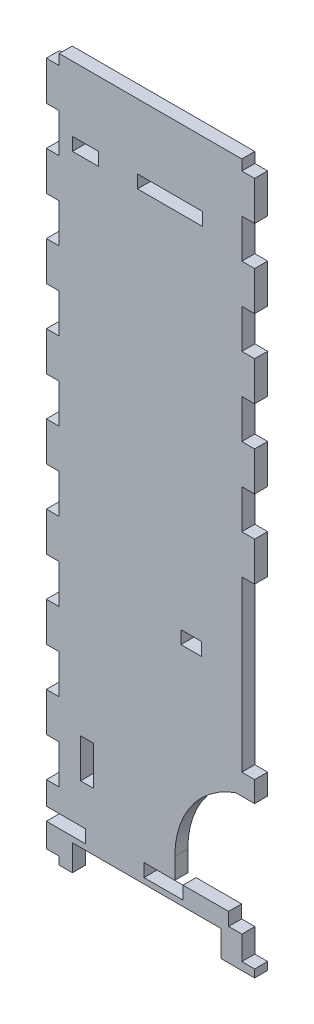
SolidWorks part; units mm, degrees
material "Balsa"
ref_plane "Plan de face" through (0, 0, 0) normal (0, 0, 1) x (1, 0, 0)
ref_plane "Plan de dessus" through (0, 0, 0) normal (0, 1, 0) x (1, 0, 0)
ref_plane "Plan de droite" through (0, 0, 0) normal (1, 0, 0) x (0, 0, -1)
sketch "Esquisse1" plane through (0, 0, 0) normal (0, 0, 1) x (1, 0, 0)
  line L0 (49.3309, 25.1093) -> (120.4109, 25.1093) construction
  line L1 (0, 0) -> (80, 0)
  line L2 (0, 0) -> (0, 270)
  line L3 (0, 270) -> (80, 270)
  line L4 (80, 59.7791) -> (80, 270)
  line L5 (49.3309, 25.1093) -> (49.3309, 17.15)
  line L6 (49.3309, 17.15) -> (80, 17.15)
  line L7 (80, 17.15) -> (80, 0)
  ellipse E0 centre (84.8709, 25.1093) end of major axis (120.4109, 25.1093) minor radius 35 (49.3309, 25.1093) -> (80, 59.7791) cw
  point P5 (84.8709, 25.1093)
  dimension "D1" = 80
  dimension "D2" = 270
  dimension "D3" = 80
  dimension "D4" = 70
  dimension "D5" = 71.08
extrude "Boss.-Extru.1" add sketch "Esquisse1" along normal blind 5
sketch "Esquisse2" plane through (0, 0, 5) normal (0, 0, 1) x (1, 0, 0)
  line L0 (80, 0) -> (80, 17.15) construction
  line L1 (51.6797, 101.7504) -> (59.6797, 101.7504)
  line L2 (51.6797, 101.7504) -> (51.6797, 96.7504)
  line L3 (51.6797, 96.7504) -> (59.6797, 96.7504)
  line L4 (59.6797, 101.7504) -> (59.6797, 96.7504)
  line L5 (75.08, 12.15) -> (70, 12.15)
  line L6 (80, 17.15) -> (80, 3)
  line L7 (80, 3) -> (75.08, 3)
  line L8 (75.08, 12.15) -> (75.08, 3)
  line L9 (80, 59.7791) -> (80, 270) construction
  line L10 (0, 0) -> (80, 0) construction
  line L11 (70, 12.15) -> (70, 17.15)
  line L12 (80, 17.15) -> (49.3309, 17.15) construction
  line L13 (70, 17.15) -> (80, 17.15)
  line L14 (0, 270) -> (0, 0) construction
  line L15 (37.5, 17.15) -> (52.5, 17.15)
  line L16 (37.5, 17.15) -> (37.5, 12.15)
  line L17 (37.5, 12.15) -> (52.5, 12.15)
  line L18 (52.5, 17.15) -> (52.5, 12.15)
  line L19 (15, 17.15) -> (0, 17.15)
  line L20 (15, 17.15) -> (15, 12.15)
  line L21 (15, 12.15) -> (0, 12.15)
  line L22 (0, 17.15) -> (0, 12.15)
  line L23 (80, 131) -> (75.08, 131)
  line L24 (0, 0) -> (4.92, 0)
  line L25 (0, 0) -> (0, 3)
  line L26 (0, 3) -> (4.92, 3)
  line L27 (4.92, 0) -> (4.92, 3)
  line L28 (80, 131) -> (80, 66)
  line L29 (80, 66) -> (75.08, 66)
  line L30 (75.08, 131) -> (75.08, 66)
  line L31 (0, 0) -> (80, 0) construction
  line L32 (80, 191) -> (75.08, 191)
  line L33 (80, 161) -> (75.08, 161)
  line L34 (80, 161) -> (80, 146)
  line L35 (80, 146) -> (75.08, 146)
  line L36 (75.08, 161) -> (75.08, 146)
  line L37 (80, 191) -> (80, 176)
  line L38 (80, 176) -> (75.08, 176)
  line L39 (75.08, 191) -> (75.08, 176)
  line L40 (80, 221) -> (75.08, 221)
  line L41 (80, 221) -> (80, 206)
  line L42 (80, 206) -> (75.08, 206)
  line L43 (75.08, 221) -> (75.08, 206)
  line L44 (80, 251) -> (75.08, 251)
  line L45 (80, 251) -> (80, 236)
  line L46 (80, 236) -> (75.08, 236)
  line L47 (75.08, 251) -> (75.08, 236)
  line L48 (80, 281) -> (75.08, 281)
  line L49 (80, 281) -> (80, 266)
  line L50 (80, 266) -> (75.08, 266)
  line L51 (75.08, 281) -> (75.08, 266)
  line L52 (0, 270) -> (0, 0) construction
  line L53 (0, 266) -> (4.92, 266)
  line L54 (0, 266) -> (0, 281)
  line L55 (0, 281) -> (4.92, 281)
  line L56 (4.92, 266) -> (4.92, 281)
  line L57 (80, 270) -> (0, 270) construction
  line L58 (0, 236) -> (4.92, 236)
  line L59 (0, 236) -> (0, 251)
  line L60 (0, 251) -> (4.92, 251)
  line L61 (4.92, 236) -> (4.92, 251)
  line L62 (0, 206) -> (4.92, 206)
  line L63 (0, 206) -> (0, 221)
  line L64 (0, 221) -> (4.92, 221)
  line L65 (4.92, 206) -> (4.92, 221)
  line L66 (0, 176) -> (4.92, 176)
  line L67 (0, 176) -> (0, 191)
  line L68 (0, 191) -> (4.92, 191)
  line L69 (4.92, 176) -> (4.92, 191)
  line L70 (0, 146) -> (4.92, 146)
  line L71 (0, 146) -> (0, 161)
  line L72 (0, 161) -> (4.92, 161)
  line L73 (4.92, 146) -> (4.92, 161)
  line L74 (0, 116) -> (4.92, 116)
  line L75 (0, 116) -> (0, 131)
  line L76 (0, 131) -> (4.92, 131)
  line L77 (4.92, 116) -> (4.92, 131)
  line L78 (0, 86) -> (4.92, 86)
  line L79 (0, 86) -> (0, 101)
  line L80 (0, 101) -> (4.92, 101)
  line L81 (4.92, 86) -> (4.92, 101)
  line L82 (0, 56) -> (4.92, 56)
  line L83 (0, 56) -> (0, 71)
  line L84 (0, 71) -> (4.92, 71)
  line L85 (4.92, 56) -> (4.92, 71)
  line L86 (0, 26) -> (4.92, 26)
  line L87 (0, 26) -> (0, 41)
  line L88 (0, 41) -> (4.92, 41)
  line L89 (4.92, 26) -> (4.92, 41)
  line L91 (10, 240) -> (20, 240)
  line L92 (10, 240) -> (10, 245)
  line L93 (10, 245) -> (20, 245)
  line L94 (20, 240) -> (20, 245)
  line L95 (80, 270) -> (0, 270) construction
  line L96 (35, 240) -> (60, 240)
  line L97 (35, 240) -> (35, 245)
  line L98 (35, 245) -> (60, 245)
  line L99 (60, 240) -> (60, 245)
  dimension "D1" = 4.92
  dimension "D2" = 3
  dimension "D3" = 10
  dimension "D4" = 5
  dimension "D5" = 5
  dimension "D6" = 15
  dimension "D7" = 27.5
  dimension "D8" = 5
  dimension "D9" = 15
  dimension "D10" = 4.92
  dimension "D11" = 3
  dimension "D12" = 4.92
  dimension "D13" = 66
  dimension "D14" = 65
  dimension "D15" = 15
  dimension "D16" = 15
  dimension "D18" = 15
  dimension "D19" = 4
  dimension "D21" = 5
  dimension "D22" = 25
  dimension "D17" = 5
  dimension "D20" = 9
extrude "Enlèv. mat.-Extru.1" cut sketch "Esquisse2" against normal blind 5
sketch "Esquisse3" plane through (0, 0, 0) normal (0, 0, -1) x (-1, 0, 0)
  line L0 (-80, 59.7791) -> (-80, 66) construction
  line L1 (-80, 61.9473) -> (-72.7194, 61.9473)
  line L2 (-80, 61.9473) -> (-80, 58)
  line L3 (-80, 58) -> (-72.7194, 58)
  line L4 (-72.7194, 61.9473) -> (-72.7194, 58)
  line L5 (-4.92, 0) -> (-80, 0) construction
  ellipse E0 centre (-84.8709, 25.1093) end of major axis (-120.4109, 25.1093) minor radius 35 (-49.3309, 25.1093) -> (-80, 59.7791) ccw construction
  dimension "D1" = 58
extrude "Boss.-Extru.2" add sketch "Esquisse3" against normal blind 5
sketch "Esquisse4" plane through (0, 0, 5) normal (0, 0, 1) x (1, 0, 0)
  line L0 (4.92, 0) -> (80, 0) construction
  line L1 (10, 0) -> (67, 0)
  line L2 (10, 0) -> (10, 10)
  line L3 (10, 10) -> (67, 10)
  line L4 (67, 0) -> (67, 10)
  line L5 (0, 12.15) -> (0, 3) construction
  line L6 (80, 0) -> (80, 3) construction
  line L8 (13.1283, 47.15) -> (18.1283, 47.15)
  line L9 (13.1283, 47.15) -> (13.1283, 32.15)
  line L10 (13.1283, 32.15) -> (18.1283, 32.15)
  line L11 (18.1283, 47.15) -> (18.1283, 32.15)
  dimension "D1" = 10
  dimension "D2" = 10
  dimension "D3" = 13
extrude "Enlèv. mat.-Extru.2" cut sketch "Esquisse4" against normal blind 5
